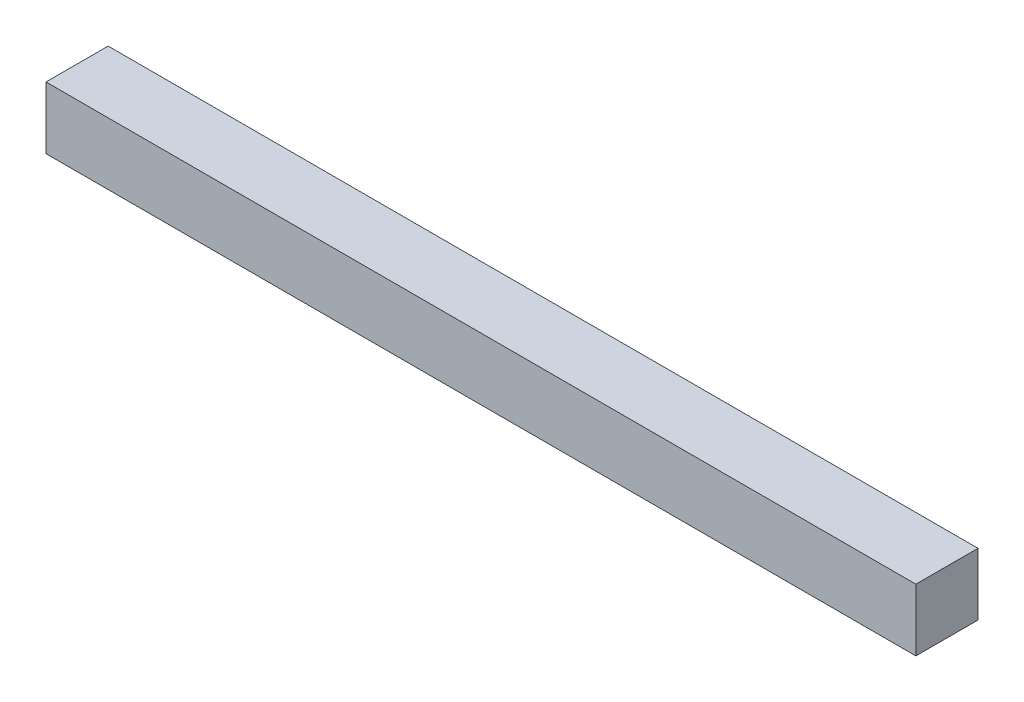
SolidWorks part; units mm, degrees
ref_plane "Front Plane" through (0, 0, 0) normal (0, 0, 1) x (1, 0, 0)
ref_plane "Top Plane" through (0, 0, 0) normal (0, 1, 0) x (1, 0, 0)
ref_plane "Right Plane" through (0, 0, 0) normal (1, 0, 0) x (0, 0, -1)
sketch "Belt Drive Axle" plane through (0, 0, 0) normal (0, 1, 0) x (1, 0, 0)
  line L1 (-44.45, -3.175) -> (44.45, -3.175)
  line L2 (-44.45, -3.175) -> (-44.45, 3.175)
  line L3 (-44.45, 3.175) -> (44.45, 3.175)
  line L4 (44.45, -3.175) -> (44.45, 3.175)
  line L5 (-44.45, -3.175) -> (44.45, 3.175) construction
  line L6 (-44.45, 3.175) -> (44.45, -3.175) construction
  point P0 (0, 0)
  dimension "D1" = 6.35
  dimension "D2" = 88.9
extrude "Boss-Extrude1" add sketch "Belt Drive Axle" along normal blind 6.35
equation "\"Ball Diameter\"= 1.75in"
equation "\"Sheet Thickness\"= 0.25in"
equation "\"Screw Diameter\"= .17in"
equation "\"Robot Diameter\"= 16in"
equation "\"Castor Screw Diameter\"= 0.22in"
equation "\"Wheel Diameter\" = 4in"
equation "\"Nut Diameter\" = 8.4mm"
equation "\"Nut Height\" = 2.9mm"
equation "\"Screw Height\" = 0.55in"
equation "\"Pulley Diameter\" = 1in"
equation "\"Reactor Height\" = 14in"
equation "\"D1@Belt Drive Axle\"=\"Sheet Thickness\""
equation "\"Elevator Height\" = 11.5in"
equation "\"Elevator Width\" = \"Ball Diameter\" + 0.25in"
equation "\"Elevator Axle Length\" = \"Elevator Width\" + 6*\"Sheet Thickness\""
equation "\"D2@Belt Drive Axle\"=\"Elevator Axle Length\""
equation "\"D1@Boss-Extrude1\"=\"Sheet Thickness\""
